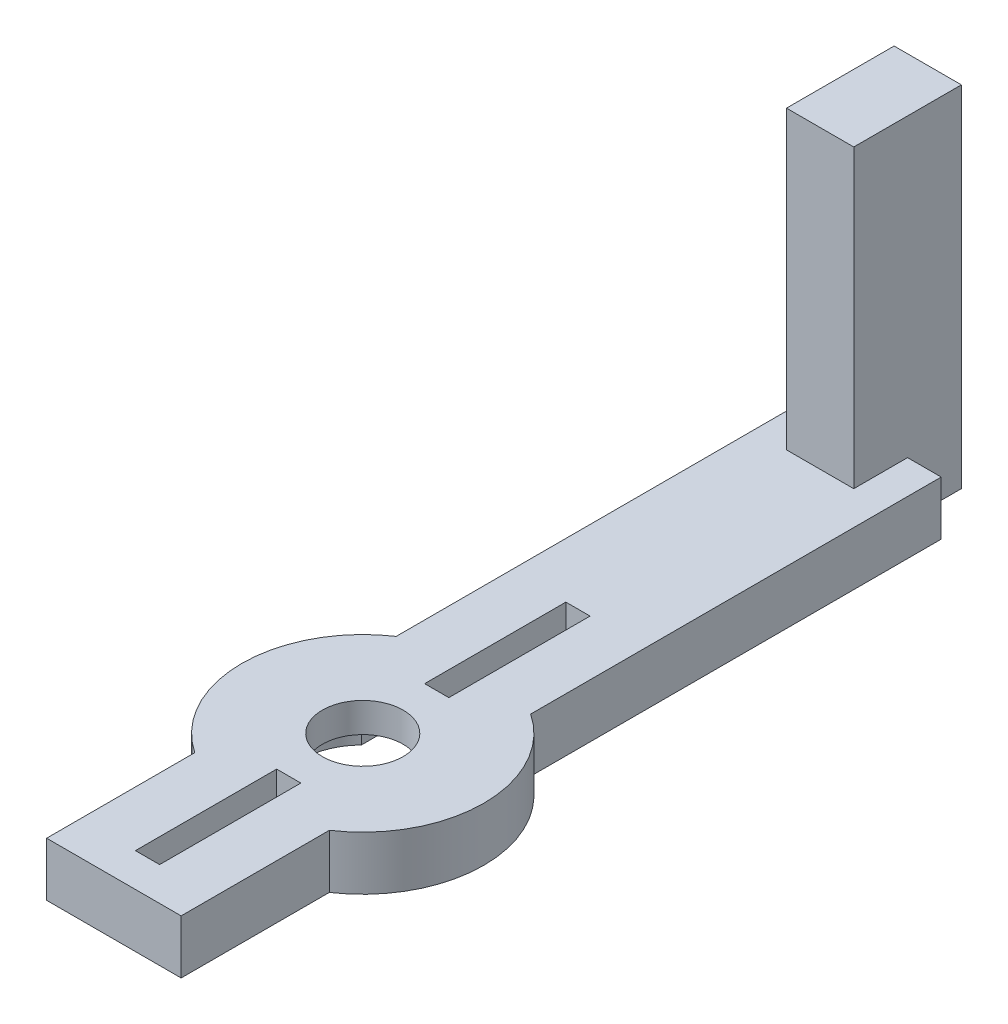
SolidWorks part; units mm, degrees
ref_plane "Front Plane" through (0, 0, 0) normal (0, 0, 1) x (1, 0, 0)
ref_plane "Top Plane" through (0, 0, 0) normal (0, 1, 0) x (1, 0, 0)
ref_plane "Right Plane" through (0, 0, 0) normal (1, 0, 0) x (0, 0, -1)
sketch "Sketch1" plane through (0, 0, 0) normal (0, 1, 0) x (1, 0, 0)
  circle A0 centre (0, 62) radius 9
extrude "Boss-Extrude1" add sketch "Sketch1" along normal blind 4 from offset 63.6
sketch "Sketch2" plane through (0, 0, 0) normal (0, 0, 1) x (1, 0, 0)
  line L1 (-5, 63.6) -> (5, 63.6)
  line L2 (-5, 63.6) -> (-5, 67.6)
  line L3 (-5, 67.6) -> (5, 67.6)
  line L4 (5, 63.6) -> (5, 67.6)
extrude "Boss-Extrude2" add sketch "Sketch2" along normal blind 56.5 from offset 100 offset against normal yes
sketch "Sketch3" plane through (0, 0, 0) normal (0, 0, 1) x (1, 0, 0)
  line L1 (-2.5, 63.6) -> (2.5, 63.6)
  line L2 (-2.5, 63.6) -> (-2.5, 89.6)
  line L3 (-2.5, 89.6) -> (2.5, 89.6)
  line L4 (2.5, 63.6) -> (2.5, 89.6)
extrude "Boss-Extrude3" add sketch "Sketch3" along normal blind 8 from offset 104 offset against normal yes
sketch "Sketch4" plane through (0, 0, 0) normal (0, 1, 0) x (1, 0, 0)
  circle A0 centre (0, 62) radius 4.6
extrude "Boss-Extrude4" add sketch "Sketch4" along normal blind 2.3 from offset 63.1 separate body
combine bodies "Combine1" operation type subtract main body 103 bodies to subtract 104
sketch "Sketch5" plane through (0, 0, 0) normal (0, 0, 1) x (1, 0, 0)
  line L1 (-3.3, 63.1) -> (3.3, 63.1)
  line L2 (-3.3, 63.1) -> (-3.3, 65.4)
  line L3 (-3.3, 65.4) -> (3.3, 65.4)
  line L4 (3.3, 63.1) -> (3.3, 65.4)
extrude "Boss-Extrude5" add sketch "Sketch5" along normal blind 17.5 from offset 62 separate body offset against normal yes
combine bodies "Combine2" operation type subtract main body 105 bodies to subtract 106
sketch "Sketch6" plane through (0, 0, 0) normal (0, 0, 1) x (1, 0, 0)
  line L1 (-0.9, 62.6) -> (0.9, 62.6)
  line L2 (-0.9, 62.6) -> (-0.9, 68.6)
  line L3 (-0.9, 68.6) -> (0.9, 68.6)
  line L4 (0.9, 62.6) -> (0.9, 68.6)
extrude "Boss-Extrude6" add sketch "Sketch6" along normal blind 10.5 from offset 56.5 separate body offset against normal yes
combine bodies "Combine3" operation type subtract main body 107 bodies to subtract 108
sketch "Sketch7" plane through (0, 0, 0) normal (0, 0, 1) x (1, 0, 0)
  line L1 (-3.3, 63.1) -> (3.3, 63.1)
  line L2 (-3.3, 63.1) -> (-3.3, 65.4)
  line L3 (-3.3, 65.4) -> (3.3, 65.4)
  line L4 (3.3, 63.1) -> (3.3, 65.4)
extrude "Boss-Extrude7" add sketch "Sketch7" along normal blind 17.5 from offset 79.5 separate body offset against normal yes
combine bodies "Combine4" operation type subtract main body 109 bodies to subtract 110
sketch "Sketch8" plane through (0, 0, 0) normal (0, 0, 1) x (1, 0, 0)
  line L1 (-0.9, 62.6) -> (0.9, 62.6)
  line L2 (-0.9, 62.6) -> (-0.9, 68.6)
  line L3 (-0.9, 68.6) -> (0.9, 68.6)
  line L4 (0.9, 62.6) -> (0.9, 68.6)
extrude "Boss-Extrude8" add sketch "Sketch8" along normal blind 10.5 from offset 78 separate body offset against normal yes
combine bodies "Combine5" operation type subtract main body 111 bodies to subtract 112
sketch "Sketch9" plane through (0, 0, 0) normal (0, 1, 0) x (1, 0, 0)
  circle A0 centre (0, 62) radius 3
extrude "Boss-Extrude9" add sketch "Sketch9" along normal blind 6 from offset 62.6 separate body
combine bodies "Combine6" operation type subtract main body 113 bodies to subtract 114
